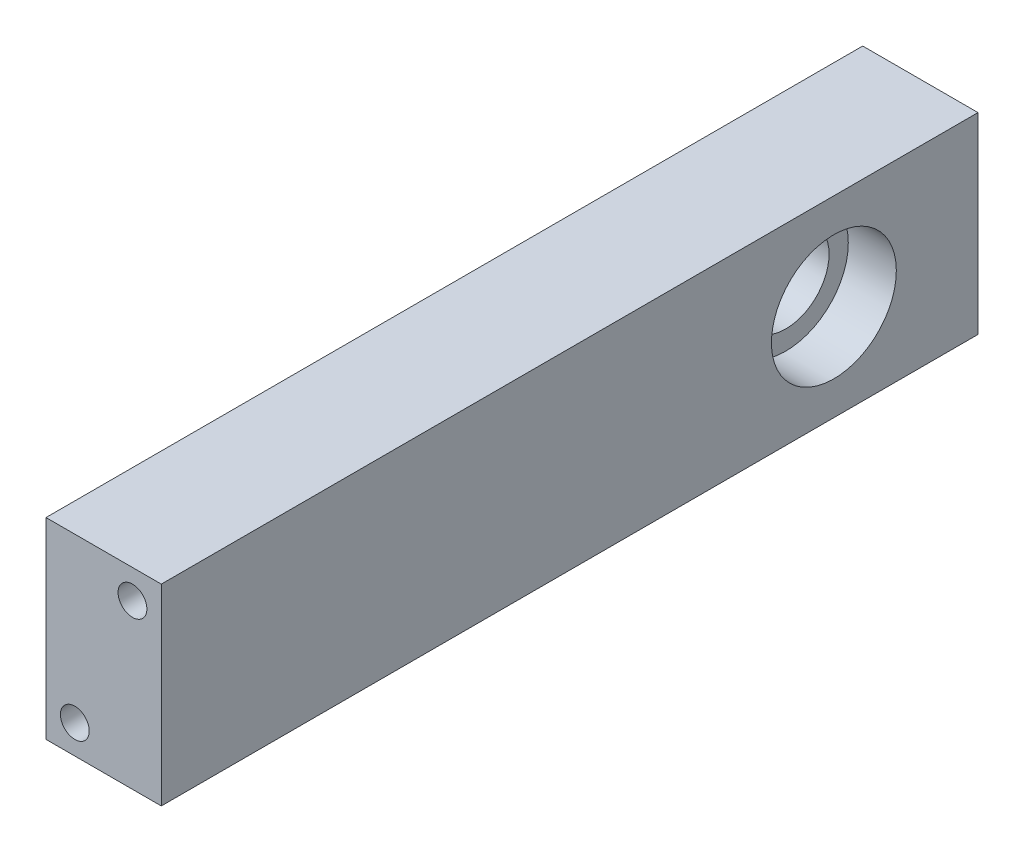
SolidWorks part; units mm, degrees
ref_plane "Płaszczyzna przednia" through (0, 0, 0) normal (0, 0, 1) x (1, 0, 0)
ref_plane "Płaszczyzna górna" through (0, 0, 0) normal (0, 1, 0) x (1, 0, 0)
ref_plane "Płaszczyzna prawa" through (0, 0, 0) normal (1, 0, 0) x (0, 0, -1)
sketch "Szkic1" plane through (0, 0, 0) normal (0, 0, 1) x (1, 0, 0)
  line L1 (-6, -10) -> (6, -10)
  line L2 (-6, -10) -> (-6, 10)
  line L3 (-6, 10) -> (6, 10)
  line L4 (6, -10) -> (6, 10)
  line L5 (-6, -10) -> (6, 10) construction
  line L6 (-6, 10) -> (6, -10) construction
  point P0 (0, 0)
  dimension "D1" = 20
  dimension "D2" = 12
extrude "Dodanie-wyciągnięcie1" add sketch "Szkic1" along normal blind 85
sketch "Szkic2" plane through (0, 0, 85) normal (0, 0, 1) x (1, 0, 0)
  line L0 (6, -10) -> (6, 10) construction
  line L3 (6, 10) -> (-6, 10) construction
  line L5 (-6, -10) -> (6, -10) construction
  line L6 (-6, 10) -> (-6, -10) construction
  circle A0 centre (3, 7) radius 1.5
  circle A1 centre (-3, -7) radius 1.5
  dimension "D1" = 3
  dimension "D2" = 3
  dimension "D3" = 3
  dimension "D4" = 3
  dimension "D5" = 3
  dimension "D6" = 3
extrude "Wytnij-wyciągnięcie1" cut sketch "Szkic2" against normal blind 10
sketch "Szkic5" plane through (6, 0, 0) normal (1, 0, 0) x (0, 0, -1)
  line L0 (-85, -10) -> (0, -10) construction
  line L1 (-85, -10) -> (-85, 10) construction
  circle A0 centre (-15, 0) radius 6.5
  dimension "D1" = 13
  dimension "D2" = 10
  dimension "D3" = 70
extrude "Wytnij-wyciągnięcie4" cut sketch "Szkic5" against normal blind 5
sketch "Szkic6" plane through (-6, 0, 0) normal (-1, 0, 0) x (0, 0, 1)
  line L0 (85, -10) -> (0, -10) construction
  line L1 (85, 10) -> (85, -10) construction
  circle A0 centre (15, 0) radius 4.5
  dimension "D1" = 9
  dimension "D2" = 10
  dimension "D3" = 70
extrude "Wytnij-wyciągnięcie5" cut sketch "Szkic6" against normal through all
